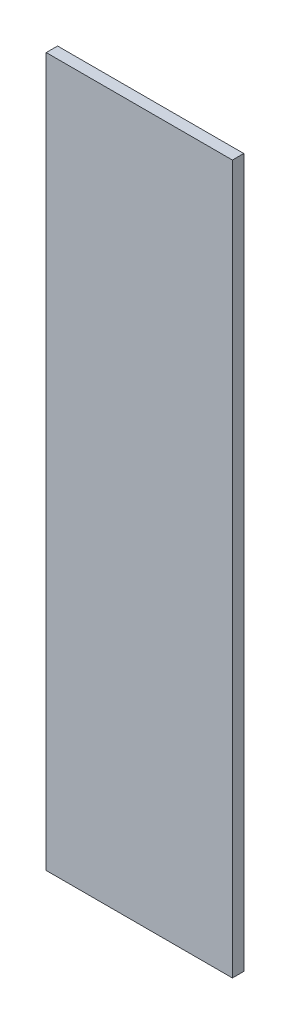
SolidWorks part; units mm, degrees
ref_plane "Front Plane" through (0, 0, 0) normal (0, 0, 1) x (1, 0, 0)
ref_plane "Top Plane" through (0, 0, 0) normal (0, 1, 0) x (1, 0, 0)
ref_plane "Right Plane" through (0, 0, 0) normal (1, 0, 0) x (0, 0, -1)
sketch "Sketch1" plane through (0, 0, 0) normal (0, 0, 1) x (1, 0, 0)
  line L1 (-41, -156) -> (41, -156)
  line L2 (-41, -156) -> (-41, 156)
  line L3 (-41, 156) -> (41, 156)
  line L4 (41, -156) -> (41, 156)
  line L5 (-41, -156) -> (41, 156) construction
  line L6 (-41, 156) -> (41, -156) construction
  point P0 (0, 0)
  dimension "D1" = 312
  dimension "D2" = 82
extrude "Boss-Extrude1" add sketch "Sketch1" along normal blind 5
